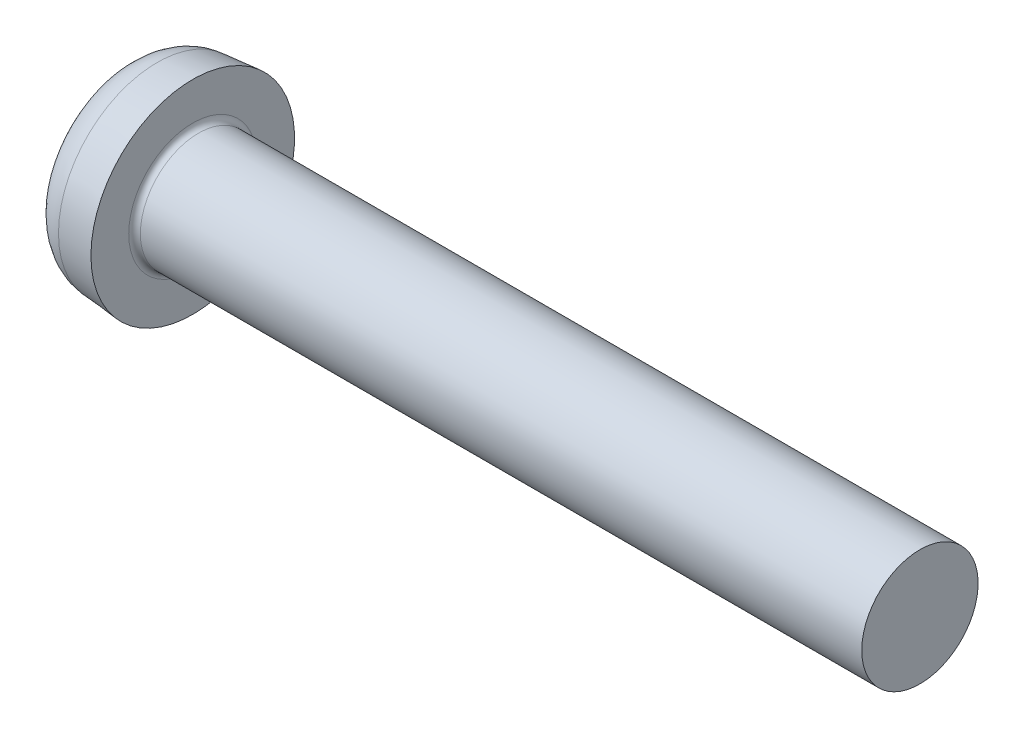
SolidWorks part; units mm, degrees
ref_plane "Front Plane" through (0, 0, 0) normal (0, 0, 1) x (1, 0, 0)
ref_plane "Top Plane" through (0, 0, 0) normal (0, 1, 0) x (1, 0, 0)
ref_plane "Right Plane" through (0, 0, 0) normal (1, 0, 0) x (0, 0, -1)
sketch "BodySke" plane through (0, 0, 0) normal (0, 0, 1) x (1, 0, 0)
  line L0 (0, 0) -> (111.3824, 0) construction
  line L1 (0, 0) -> (0, 8) construction
  line L2 (5.4, 4) -> (5.4, 7)
  line L3 (5.4, 7) -> (2.9561, 6.7862)
  line L4 (5.4, 4) -> (55.4, 4)
  line L5 (55.4, 4) -> (55.4, 0)
  line L6 (6.65, 7.824) -> (6.65, -6.8939) construction
  line L7 (0, 0) -> (55.4, 0)
  line L8 (25.4, 8.824) -> (25.4, -4.958) construction
  arc A0 (2.9561, 6.7862) -> (0.6811, 4.9045) centre (3.1827, 4.1961) ccw
  arc A1 (0.6811, 4.9045) -> (0, 0) centre (18, 0) ccw
  point P10 (55.4, 3.4455)
  dimension "Thread_minor" = 6.891
  dimension "Head_height" = 5.4
  dimension "Advance" = 1.25
  dimension "Length" = 50
  dimension "D1" = 5
  dimension "Head_dia" = 14
revolve "BaseBody" add sketch "BodySke" angle 360 about L0
cosmetic thread "ThreadCosmetic" [suppressed] parameters "Thread_minor"=6.891
fillet "Fillet1" radius 0.4 1 edges at (5.4, 0, 4)
ref_plane "Plane1" through (4.36, 0, 0) normal (1, 0, 0) x (0, 0, -1)
sketch "RecSkeTop" plane through (0, 0, 0) normal (1, 0, 0) x (0, 0, -1)
  line L1 (-0.858, 3.9) -> (0.858, 3.9)
  line L2 (-0.858, 3.9) -> (-0.858, -3.9)
  line L3 (-0.858, -3.9) -> (0.858, -3.9)
  line L4 (0.858, 3.9) -> (0.858, -3.9)
  dimension "D1" = 3.9
  dimension "D2" = 1.716
  dimension "D3" = 0.858
sketch "RecSkeBot" plane through (4.36, 0, 0) normal (1, 0, 0) x (0, 0, -1)
  line L0 (-0.858, 3.9) -> (-0.858, -3.9) construction
  line L1 (-0.858, 1.7262) -> (0.858, 1.7262)
  line L2 (-0.858, 1.7262) -> (-0.858, -1.7262)
  line L3 (-0.858, -1.7262) -> (0.858, -1.7262)
  line L4 (0.858, 1.7262) -> (0.858, -1.7262)
  line L5 (0.858, 3.9) -> (0.858, -3.9) construction
  dimension "D1" = 3.4524
  dimension "D2" = 1.7262
loft "Recess" cut profiles "RecSkeTop", "RecSkeBot" connector at (0, -3.9, 0.858) connector at (4.36, -1.7262, 0.858)
pattern_circular "RecPat" count 2 every 90 about axis through (0, 0, 0) along (1, 0, 0) of "Recess"
sketch "RecCorSke" plane through (0, 0, 0) normal (0, 0, 1) x (1, 0, 0)
  line L0 (0, 0) -> (57.5987, 0) construction
  line L1 (0, 0) -> (0, 1.8876)
  line L3 (0, 1.8876) -> (4.36, 1.5827)
  line L4 (4.36, 1.5827) -> (4.8743, 0)
  line L5 (4.8743, 0) -> (0, 0)
  dimension "D1" = 18
  dimension "D2" = 4.36
  dimension "D3" = 1.8876
  dimension "D4" = 4
revolve "RecessCore" cut sketch "RecCorSke" angle 360 about L0
sketch "ThdSchSke" plane through (0, 0, 0) normal (0, 0, 1) x (1, 0, 0)
  line L0 (0, 0) -> (55.1256, 0) construction
  line L1 (0, 0) -> (111.3824, 0) construction
  line L2 (55.0799, 4) -> (55.0799, 4.6403)
  line L3 (55.0799, 4.6403) -> (55.7201, 4.6403)
  line L4 (55.7201, 4.6403) -> (55.7201, 4)
  line L5 (55.7201, 4) -> (55.4, 3.4455)
  line L6 (55.4, 3.4455) -> (55.0799, 4)
  line L7 (5.4, 4) -> (55.4, 4) construction
  line L13 (55.4, 4) -> (55.4, 0) construction
revolve "ThreadSchematic" [suppressed] cut sketch "ThdSchSke" angle 360 about L0
pattern_linear "ThdSchPat" [suppressed] count 24 along (-1, 0, 0) of bodies 103
equation "\"Thread_minor@ThreadCosmetic\" = \"Thread_minor@BodySke\""
equation "\"D1@RecSkeTop\" = \"Cross_dia@RecSkeTop\" / 2"
equation "\"D2@RecSkeTop\" = \"Cross_dia@RecSkeTop\" * 0.22"
equation "\"D3@RecSkeTop\" = \"D2@RecSkeTop\" / 2"
equation "\"D1@RecSkeBot\" = \"Cross_dia@RecSkeTop\" - 2 * \"Cross_depth@Plane1\" *  tan( 26.5 * 0.017453292 ) "
equation "\"D2@RecSkeBot\" = \"D1@RecSkeBot\" / 2"
equation "\"D2@RecCorSke\" = \"Cross_depth@Plane1\""
equation "\"D3@RecCorSke\" = \"D2@RecSkeTop\" * 1.1"
equation "\"Advance@ThdSchPat\" = \"Advance@BodySke\""
equation "\"D1@ThdSchPat\" =  int( \"Thread_length@BodySke\" / \"Advance@ThdSchPat\" ) "
